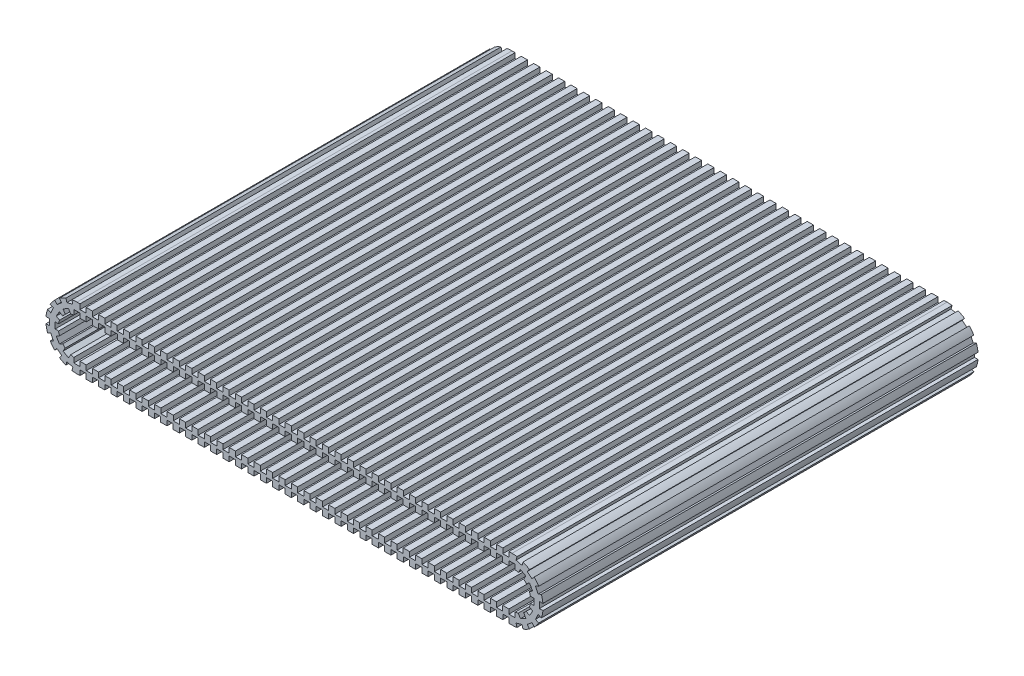
SolidWorks part; units mm, degrees
ref_plane "前视基准面" through (0, 0, 0) normal (0, 0, 1) x (1, 0, 0)
ref_plane "上视基准面" through (0, 0, 0) normal (0, 1, 0) x (1, 0, 0)
ref_plane "右视基准面" through (0, 0, 0) normal (1, 0, 0) x (0, 0, -1)
sketch "草图1" plane through (0, 0, 0) normal (0, 0, 1) x (1, 0, 0)
  line L0 (-175, 0) -> (175, 0) construction
  line L1 (-175, 25) -> (175, 25)
  line L2 (-175, -25) -> (175, -25)
  line L3 (-175, 0) -> (175, 0) construction
  line L4 (-175, 15) -> (175, 15)
  line L5 (-175, -15) -> (175, -15)
  arc A0 (-175, 25) -> (-175, -25) centre (-175, 0) ccw
  arc A1 (175, -25) -> (175, 25) centre (175, 0) ccw
  arc A2 (-175, 15) -> (-175, -15) centre (-175, 0) ccw
  arc A3 (175, -15) -> (175, 15) centre (175, 0) ccw
  point P3 (0, 0)
  point P8 (0, 0)
  dimension "D2" = 15
  dimension "D3" = 25
  dimension "D1" = 350
extrude "凸台-拉伸1" add sketch "草图1" along normal blind 350
sketch "草图2" plane through (0, 0, 350) normal (0, 0, 1) x (1, 0, 0)
  line L0 (-2.5, 25) -> (-2.5, 21)
  line L1 (175, 25) -> (-175, 25) construction
  line L2 (-2.5, 21) -> (2.5, 21)
  line L3 (2.5, 21) -> (2.5, 25)
  line L4 (-2.5, 25) -> (2.5, 25)
  line L5 (-12.5065, 25) -> (-7.5065, 25)
  line L6 (-7.5065, 21) -> (-7.5065, 25)
  line L7 (-12.5065, 21) -> (-7.5065, 21)
  line L8 (-12.5065, 25) -> (-12.5065, 21)
  line L9 (-22.513, 25) -> (-17.513, 25)
  line L10 (-17.513, 21) -> (-17.513, 25)
  line L11 (-22.513, 21) -> (-17.513, 21)
  line L12 (-22.513, 25) -> (-22.513, 21)
  line L13 (-32.5195, 25) -> (-27.5195, 25)
  line L14 (-27.5195, 21) -> (-27.5195, 25)
  line L15 (-32.5195, 21) -> (-27.5195, 21)
  line L16 (-32.5195, 25) -> (-32.5195, 21)
  line L17 (-42.526, 25) -> (-37.526, 25)
  line L18 (-37.526, 21) -> (-37.526, 25)
  line L19 (-42.526, 21) -> (-37.526, 21)
  line L20 (-42.526, 25) -> (-42.526, 21)
  line L21 (-52.5325, 25) -> (-47.5325, 25)
  line L22 (-47.5325, 21) -> (-47.5325, 25)
  line L23 (-52.5325, 21) -> (-47.5325, 21)
  line L24 (-52.5325, 25) -> (-52.5325, 21)
  line L25 (-62.539, 25) -> (-57.539, 25)
  line L26 (-57.539, 21) -> (-57.539, 25)
  line L27 (-62.539, 21) -> (-57.539, 21)
  line L28 (-62.539, 25) -> (-62.539, 21)
  line L29 (-72.5455, 25) -> (-67.5455, 25)
  line L30 (-67.5455, 21) -> (-67.5455, 25)
  line L31 (-72.5455, 21) -> (-67.5455, 21)
  line L32 (-72.5455, 25) -> (-72.5455, 21)
  line L33 (-82.552, 25) -> (-77.552, 25)
  line L34 (-77.552, 21) -> (-77.552, 25)
  line L35 (-82.552, 21) -> (-77.552, 21)
  line L36 (-82.552, 25) -> (-82.552, 21)
  line L37 (-92.5585, 25) -> (-87.5585, 25)
  line L38 (-87.5585, 21) -> (-87.5585, 25)
  line L39 (-92.5585, 21) -> (-87.5585, 21)
  line L40 (-92.5585, 25) -> (-92.5585, 21)
  line L41 (-102.5649, 25) -> (-97.5649, 25)
  line L42 (-97.5649, 21) -> (-97.5649, 25)
  line L43 (-102.5649, 21) -> (-97.5649, 21)
  line L44 (-102.5649, 25) -> (-102.5649, 21)
  line L45 (0, 0) -> (0, 11.574) construction
  line L46 (0, 0) -> (13.4491, 0) construction
  line L47 (102.5649, 25) -> (102.5649, 21)
  line L48 (102.5649, 21) -> (97.5649, 21)
  line L49 (97.5649, 21) -> (97.5649, 25)
  line L50 (102.5649, 25) -> (97.5649, 25)
  line L51 (92.5585, 25) -> (92.5585, 21)
  line L52 (92.5585, 21) -> (87.5585, 21)
  line L53 (87.5585, 21) -> (87.5585, 25)
  line L54 (92.5585, 25) -> (87.5585, 25)
  line L55 (82.552, 25) -> (82.552, 21)
  line L56 (82.552, 21) -> (77.552, 21)
  line L57 (77.552, 21) -> (77.552, 25)
  line L58 (82.552, 25) -> (77.552, 25)
  line L59 (72.5455, 25) -> (72.5455, 21)
  line L60 (72.5455, 21) -> (67.5455, 21)
  line L61 (67.5455, 21) -> (67.5455, 25)
  line L62 (72.5455, 25) -> (67.5455, 25)
  line L63 (62.539, 25) -> (62.539, 21)
  line L64 (62.539, 21) -> (57.539, 21)
  line L65 (57.539, 21) -> (57.539, 25)
  line L66 (62.539, 25) -> (57.539, 25)
  line L67 (52.5325, 25) -> (52.5325, 21)
  line L68 (52.5325, 21) -> (47.5325, 21)
  line L69 (47.5325, 21) -> (47.5325, 25)
  line L70 (52.5325, 25) -> (47.5325, 25)
  line L71 (42.526, 25) -> (42.526, 21)
  line L72 (42.526, 21) -> (37.526, 21)
  line L73 (37.526, 21) -> (37.526, 25)
  line L74 (42.526, 25) -> (37.526, 25)
  line L75 (32.5195, 25) -> (32.5195, 21)
  line L76 (32.5195, 21) -> (27.5195, 21)
  line L77 (27.5195, 21) -> (27.5195, 25)
  line L78 (32.5195, 25) -> (27.5195, 25)
  line L79 (22.513, 25) -> (22.513, 21)
  line L80 (22.513, 21) -> (17.513, 21)
  line L81 (17.513, 21) -> (17.513, 25)
  line L82 (22.513, 25) -> (17.513, 25)
  line L83 (12.5065, 25) -> (12.5065, 21)
  line L84 (12.5065, 21) -> (7.5065, 21)
  line L85 (7.5065, 21) -> (7.5065, 25)
  line L86 (12.5065, 25) -> (7.5065, 25)
  line L87 (-7.5065, 15) -> (-7.5065, 19)
  line L88 (175, 15) -> (-175, 15) construction
  line L89 (-7.5065, 19) -> (-2.5065, 19)
  line L90 (-2.5065, 19) -> (-2.5065, 15)
  line L91 (-2.5065, 15) -> (-7.5065, 15)
  line L92 (-12.5065, 15) -> (-17.5065, 15)
  line L93 (-17.5065, 15) -> (-17.5065, 19)
  line L94 (-17.5065, 19) -> (-12.5065, 19)
  line L95 (-12.5065, 19) -> (-12.5065, 15)
  line L96 (-22.5065, 15) -> (-27.5065, 15)
  line L97 (-27.5065, 15) -> (-27.5065, 19)
  line L98 (-27.5065, 19) -> (-22.5065, 19)
  line L99 (-22.5065, 19) -> (-22.5065, 15)
  line L100 (-32.5065, 15) -> (-37.5065, 15)
  line L101 (-37.5065, 15) -> (-37.5065, 19)
  line L102 (-37.5065, 19) -> (-32.5065, 19)
  line L103 (-32.5065, 19) -> (-32.5065, 15)
  line L104 (-42.5065, 15) -> (-47.5065, 15)
  line L105 (-47.5065, 15) -> (-47.5065, 19)
  line L106 (-47.5065, 19) -> (-42.5065, 19)
  line L107 (-42.5065, 19) -> (-42.5065, 15)
  line L108 (-52.5065, 15) -> (-57.5065, 15)
  line L109 (-57.5065, 15) -> (-57.5065, 19)
  line L110 (-57.5065, 19) -> (-52.5065, 19)
  line L111 (-52.5065, 19) -> (-52.5065, 15)
  line L112 (-62.5065, 15) -> (-67.5065, 15)
  line L113 (-67.5065, 15) -> (-67.5065, 19)
  line L114 (-67.5065, 19) -> (-62.5065, 19)
  line L115 (-62.5065, 19) -> (-62.5065, 15)
  line L116 (-72.5065, 15) -> (-77.5065, 15)
  line L117 (-77.5065, 15) -> (-77.5065, 19)
  line L118 (-77.5065, 19) -> (-72.5065, 19)
  line L119 (-72.5065, 19) -> (-72.5065, 15)
  line L120 (-82.5065, 15) -> (-87.5065, 15)
  line L121 (-87.5065, 15) -> (-87.5065, 19)
  line L122 (-87.5065, 19) -> (-82.5065, 19)
  line L123 (-82.5065, 19) -> (-82.5065, 15)
  line L124 (-92.5065, 15) -> (-97.5065, 15)
  line L125 (-97.5065, 15) -> (-97.5065, 19)
  line L126 (-97.5065, 19) -> (-92.5065, 19)
  line L127 (-92.5065, 19) -> (-92.5065, 15)
  line L128 (92.5065, 19) -> (92.5065, 15)
  line L129 (97.5065, 19) -> (92.5065, 19)
  line L130 (97.5065, 15) -> (97.5065, 19)
  line L131 (92.5065, 15) -> (97.5065, 15)
  line L132 (82.5065, 19) -> (82.5065, 15)
  line L133 (87.5065, 19) -> (82.5065, 19)
  line L134 (87.5065, 15) -> (87.5065, 19)
  line L135 (82.5065, 15) -> (87.5065, 15)
  line L136 (72.5065, 19) -> (72.5065, 15)
  line L137 (77.5065, 19) -> (72.5065, 19)
  line L138 (77.5065, 15) -> (77.5065, 19)
  line L139 (72.5065, 15) -> (77.5065, 15)
  line L140 (62.5065, 19) -> (62.5065, 15)
  line L141 (67.5065, 19) -> (62.5065, 19)
  line L142 (67.5065, 15) -> (67.5065, 19)
  line L143 (62.5065, 15) -> (67.5065, 15)
  line L144 (52.5065, 19) -> (52.5065, 15)
  line L145 (57.5065, 19) -> (52.5065, 19)
  line L146 (57.5065, 15) -> (57.5065, 19)
  line L147 (52.5065, 15) -> (57.5065, 15)
  line L148 (42.5065, 19) -> (42.5065, 15)
  line L149 (47.5065, 19) -> (42.5065, 19)
  line L150 (47.5065, 15) -> (47.5065, 19)
  line L151 (42.5065, 15) -> (47.5065, 15)
  line L152 (32.5065, 19) -> (32.5065, 15)
  line L153 (37.5065, 19) -> (32.5065, 19)
  line L154 (37.5065, 15) -> (37.5065, 19)
  line L155 (32.5065, 15) -> (37.5065, 15)
  line L156 (22.5065, 19) -> (22.5065, 15)
  line L157 (27.5065, 19) -> (22.5065, 19)
  line L158 (27.5065, 15) -> (27.5065, 19)
  line L159 (22.5065, 15) -> (27.5065, 15)
  line L160 (12.5065, 19) -> (12.5065, 15)
  line L161 (17.5065, 19) -> (12.5065, 19)
  line L162 (17.5065, 15) -> (17.5065, 19)
  line L163 (12.5065, 15) -> (17.5065, 15)
  line L164 (2.5065, 15) -> (7.5065, 15)
  line L165 (2.5065, 19) -> (2.5065, 15)
  line L166 (7.5065, 19) -> (2.5065, 19)
  line L167 (7.5065, 15) -> (7.5065, 19)
  line L168 (7.5065, -15) -> (7.5065, -19)
  line L169 (7.5065, -19) -> (2.5065, -19)
  line L170 (2.5065, -19) -> (2.5065, -15)
  line L171 (2.5065, -15) -> (7.5065, -15)
  line L172 (12.5065, -15) -> (17.5065, -15)
  line L173 (17.5065, -15) -> (17.5065, -19)
  line L174 (17.5065, -19) -> (12.5065, -19)
  line L175 (12.5065, -19) -> (12.5065, -15)
  line L176 (22.5065, -15) -> (27.5065, -15)
  line L177 (27.5065, -15) -> (27.5065, -19)
  line L178 (27.5065, -19) -> (22.5065, -19)
  line L179 (22.5065, -19) -> (22.5065, -15)
  line L180 (32.5065, -15) -> (37.5065, -15)
  line L181 (37.5065, -15) -> (37.5065, -19)
  line L182 (37.5065, -19) -> (32.5065, -19)
  line L183 (32.5065, -19) -> (32.5065, -15)
  line L184 (42.5065, -15) -> (47.5065, -15)
  line L185 (47.5065, -15) -> (47.5065, -19)
  line L186 (47.5065, -19) -> (42.5065, -19)
  line L187 (42.5065, -19) -> (42.5065, -15)
  line L188 (52.5065, -15) -> (57.5065, -15)
  line L189 (57.5065, -15) -> (57.5065, -19)
  line L190 (57.5065, -19) -> (52.5065, -19)
  line L191 (52.5065, -19) -> (52.5065, -15)
  line L192 (62.5065, -15) -> (67.5065, -15)
  line L193 (67.5065, -15) -> (67.5065, -19)
  line L194 (67.5065, -19) -> (62.5065, -19)
  line L195 (62.5065, -19) -> (62.5065, -15)
  line L196 (72.5065, -15) -> (77.5065, -15)
  line L197 (77.5065, -15) -> (77.5065, -19)
  line L198 (77.5065, -19) -> (72.5065, -19)
  line L199 (72.5065, -19) -> (72.5065, -15)
  line L200 (82.5065, -15) -> (87.5065, -15)
  line L201 (87.5065, -15) -> (87.5065, -19)
  line L202 (87.5065, -19) -> (82.5065, -19)
  line L203 (82.5065, -19) -> (82.5065, -15)
  line L204 (92.5065, -15) -> (97.5065, -15)
  line L205 (97.5065, -15) -> (97.5065, -19)
  line L206 (97.5065, -19) -> (92.5065, -19)
  line L207 (92.5065, -19) -> (92.5065, -15)
  line L208 (-92.5065, -19) -> (-92.5065, -15)
  line L209 (-97.5065, -19) -> (-92.5065, -19)
  line L210 (-97.5065, -15) -> (-97.5065, -19)
  line L211 (-92.5065, -15) -> (-97.5065, -15)
  line L212 (-82.5065, -19) -> (-82.5065, -15)
  line L213 (-87.5065, -19) -> (-82.5065, -19)
  line L214 (-87.5065, -15) -> (-87.5065, -19)
  line L215 (-82.5065, -15) -> (-87.5065, -15)
  line L216 (-72.5065, -19) -> (-72.5065, -15)
  line L217 (-77.5065, -19) -> (-72.5065, -19)
  line L218 (-77.5065, -15) -> (-77.5065, -19)
  line L219 (-72.5065, -15) -> (-77.5065, -15)
  line L220 (-62.5065, -19) -> (-62.5065, -15)
  line L221 (-67.5065, -19) -> (-62.5065, -19)
  line L222 (-67.5065, -15) -> (-67.5065, -19)
  line L223 (-62.5065, -15) -> (-67.5065, -15)
  line L224 (-52.5065, -19) -> (-52.5065, -15)
  line L225 (-57.5065, -19) -> (-52.5065, -19)
  line L226 (-57.5065, -15) -> (-57.5065, -19)
  line L227 (-52.5065, -15) -> (-57.5065, -15)
  line L228 (-42.5065, -19) -> (-42.5065, -15)
  line L229 (-47.5065, -19) -> (-42.5065, -19)
  line L230 (-47.5065, -15) -> (-47.5065, -19)
  line L231 (-42.5065, -15) -> (-47.5065, -15)
  line L232 (-32.5065, -19) -> (-32.5065, -15)
  line L233 (-37.5065, -19) -> (-32.5065, -19)
  line L234 (-37.5065, -15) -> (-37.5065, -19)
  line L235 (-32.5065, -15) -> (-37.5065, -15)
  line L236 (-22.5065, -19) -> (-22.5065, -15)
  line L237 (-27.5065, -19) -> (-22.5065, -19)
  line L238 (-27.5065, -15) -> (-27.5065, -19)
  line L239 (-22.5065, -15) -> (-27.5065, -15)
  line L240 (-12.5065, -19) -> (-12.5065, -15)
  line L241 (-17.5065, -19) -> (-12.5065, -19)
  line L242 (-17.5065, -15) -> (-17.5065, -19)
  line L243 (-12.5065, -15) -> (-17.5065, -15)
  line L244 (-2.5065, -15) -> (-7.5065, -15)
  line L245 (-2.5065, -19) -> (-2.5065, -15)
  line L246 (-7.5065, -19) -> (-2.5065, -19)
  line L247 (-7.5065, -15) -> (-7.5065, -19)
  line L248 (12.5065, -25) -> (7.5065, -25)
  line L249 (7.5065, -21) -> (7.5065, -25)
  line L250 (12.5065, -21) -> (7.5065, -21)
  line L251 (12.5065, -25) -> (12.5065, -21)
  line L252 (22.513, -25) -> (17.513, -25)
  line L253 (17.513, -21) -> (17.513, -25)
  line L254 (22.513, -21) -> (17.513, -21)
  line L255 (22.513, -25) -> (22.513, -21)
  line L256 (32.5195, -25) -> (27.5195, -25)
  line L257 (27.5195, -21) -> (27.5195, -25)
  line L258 (32.5195, -21) -> (27.5195, -21)
  line L259 (32.5195, -25) -> (32.5195, -21)
  line L260 (42.526, -25) -> (37.526, -25)
  line L261 (37.526, -21) -> (37.526, -25)
  line L262 (42.526, -21) -> (37.526, -21)
  line L263 (42.526, -25) -> (42.526, -21)
  line L264 (52.5325, -25) -> (47.5325, -25)
  line L265 (47.5325, -21) -> (47.5325, -25)
  line L266 (52.5325, -21) -> (47.5325, -21)
  line L267 (52.5325, -25) -> (52.5325, -21)
  line L268 (62.539, -25) -> (57.539, -25)
  line L269 (57.539, -21) -> (57.539, -25)
  line L270 (62.539, -21) -> (57.539, -21)
  line L271 (62.539, -25) -> (62.539, -21)
  line L272 (72.5455, -25) -> (67.5455, -25)
  line L273 (67.5455, -21) -> (67.5455, -25)
  line L274 (72.5455, -21) -> (67.5455, -21)
  line L275 (72.5455, -25) -> (72.5455, -21)
  line L276 (82.552, -25) -> (77.552, -25)
  line L277 (77.552, -21) -> (77.552, -25)
  line L278 (82.552, -21) -> (77.552, -21)
  line L279 (82.552, -25) -> (82.552, -21)
  line L280 (92.5585, -25) -> (87.5585, -25)
  line L281 (87.5585, -21) -> (87.5585, -25)
  line L282 (92.5585, -21) -> (87.5585, -21)
  line L283 (92.5585, -25) -> (92.5585, -21)
  line L284 (102.5649, -25) -> (97.5649, -25)
  line L285 (97.5649, -21) -> (97.5649, -25)
  line L286 (102.5649, -21) -> (97.5649, -21)
  line L287 (102.5649, -25) -> (102.5649, -21)
  line L288 (-102.5649, -25) -> (-102.5649, -21)
  line L289 (-102.5649, -21) -> (-97.5649, -21)
  line L290 (-97.5649, -21) -> (-97.5649, -25)
  line L291 (-102.5649, -25) -> (-97.5649, -25)
  line L292 (-92.5585, -25) -> (-92.5585, -21)
  line L293 (-92.5585, -21) -> (-87.5585, -21)
  line L294 (-87.5585, -21) -> (-87.5585, -25)
  line L295 (-92.5585, -25) -> (-87.5585, -25)
  line L296 (-82.552, -25) -> (-82.552, -21)
  line L297 (-82.552, -21) -> (-77.552, -21)
  line L298 (-77.552, -21) -> (-77.552, -25)
  line L299 (-82.552, -25) -> (-77.552, -25)
  line L300 (-72.5455, -25) -> (-72.5455, -21)
  line L301 (-72.5455, -21) -> (-67.5455, -21)
  line L302 (-67.5455, -21) -> (-67.5455, -25)
  line L303 (-72.5455, -25) -> (-67.5455, -25)
  line L304 (-62.539, -25) -> (-62.539, -21)
  line L305 (-62.539, -21) -> (-57.539, -21)
  line L306 (-57.539, -21) -> (-57.539, -25)
  line L307 (-62.539, -25) -> (-57.539, -25)
  line L308 (-52.5325, -25) -> (-52.5325, -21)
  line L309 (-52.5325, -21) -> (-47.5325, -21)
  line L310 (-47.5325, -21) -> (-47.5325, -25)
  line L311 (-52.5325, -25) -> (-47.5325, -25)
  line L312 (-42.526, -25) -> (-42.526, -21)
  line L313 (-42.526, -21) -> (-37.526, -21)
  line L314 (-37.526, -21) -> (-37.526, -25)
  line L315 (-42.526, -25) -> (-37.526, -25)
  line L316 (-32.5195, -25) -> (-32.5195, -21)
  line L317 (-32.5195, -21) -> (-27.5195, -21)
  line L318 (-27.5195, -21) -> (-27.5195, -25)
  line L319 (-32.5195, -25) -> (-27.5195, -25)
  line L320 (-22.513, -25) -> (-22.513, -21)
  line L321 (-22.513, -21) -> (-17.513, -21)
  line L322 (-17.513, -21) -> (-17.513, -25)
  line L323 (-22.513, -25) -> (-17.513, -25)
  line L324 (-12.5065, -25) -> (-12.5065, -21)
  line L325 (-12.5065, -21) -> (-7.5065, -21)
  line L326 (-7.5065, -21) -> (-7.5065, -25)
  line L327 (-12.5065, -25) -> (-7.5065, -25)
  line L328 (-2.5, -25) -> (2.5, -25)
  line L329 (2.5, -21) -> (2.5, -25)
  line L330 (-2.5, -21) -> (2.5, -21)
  line L331 (-2.5, -25) -> (-2.5, -21)
  line L332 (-112.5649, 25) -> (-107.5649, 25)
  line L333 (-107.5649, 21) -> (-107.5649, 25)
  line L334 (-112.5649, 21) -> (-107.5649, 21)
  line L335 (-112.5649, 25) -> (-112.5649, 21)
  line L336 (-102.5065, 15) -> (-107.5065, 15)
  line L337 (-107.5065, 15) -> (-107.5065, 19)
  line L338 (-107.5065, 19) -> (-102.5065, 19)
  line L339 (-102.5065, 19) -> (-102.5065, 15)
  line L340 (-122.5649, 25) -> (-117.5649, 25)
  line L341 (-117.5649, 21) -> (-117.5649, 25)
  line L342 (-122.5649, 21) -> (-117.5649, 21)
  line L343 (-122.5649, 25) -> (-122.5649, 21)
  line L344 (-112.5065, 15) -> (-117.5065, 15)
  line L345 (-117.5065, 15) -> (-117.5065, 19)
  line L346 (-117.5065, 19) -> (-112.5065, 19)
  line L347 (-112.5065, 19) -> (-112.5065, 15)
  line L348 (-132.5649, 25) -> (-127.5649, 25)
  line L349 (-127.5649, 21) -> (-127.5649, 25)
  line L350 (-132.5649, 21) -> (-127.5649, 21)
  line L351 (-132.5649, 25) -> (-132.5649, 21)
  line L352 (-122.5065, 15) -> (-127.5065, 15)
  line L353 (-127.5065, 15) -> (-127.5065, 19)
  line L354 (-127.5065, 19) -> (-122.5065, 19)
  line L355 (-122.5065, 19) -> (-122.5065, 15)
  line L356 (-142.5649, 25) -> (-137.5649, 25)
  line L357 (-137.5649, 21) -> (-137.5649, 25)
  line L358 (-142.5649, 21) -> (-137.5649, 21)
  line L359 (-142.5649, 25) -> (-142.5649, 21)
  line L360 (-132.5065, 15) -> (-137.5065, 15)
  line L361 (-137.5065, 15) -> (-137.5065, 19)
  line L362 (-137.5065, 19) -> (-132.5065, 19)
  line L363 (-132.5065, 19) -> (-132.5065, 15)
  line L364 (-152.5649, 25) -> (-147.5649, 25)
  line L365 (-147.5649, 21) -> (-147.5649, 25)
  line L366 (-152.5649, 21) -> (-147.5649, 21)
  line L367 (-152.5649, 25) -> (-152.5649, 21)
  line L368 (-142.5065, 15) -> (-147.5065, 15)
  line L369 (-147.5065, 15) -> (-147.5065, 19)
  line L370 (-147.5065, 19) -> (-142.5065, 19)
  line L371 (-142.5065, 19) -> (-142.5065, 15)
  line L372 (-162.5649, 25) -> (-157.5649, 25)
  line L373 (-157.5649, 21) -> (-157.5649, 25)
  line L374 (-162.5649, 21) -> (-157.5649, 21)
  line L375 (-162.5649, 25) -> (-162.5649, 21)
  line L376 (-152.5065, 15) -> (-157.5065, 15)
  line L377 (-157.5065, 15) -> (-157.5065, 19)
  line L378 (-157.5065, 19) -> (-152.5065, 19)
  line L379 (-152.5065, 19) -> (-152.5065, 15)
  line L380 (-172.5649, 25) -> (-167.5649, 25)
  line L381 (-167.5649, 21) -> (-167.5649, 25)
  line L382 (-172.5649, 21) -> (-167.5649, 21)
  line L383 (-172.5649, 25) -> (-172.5649, 21)
  line L384 (-162.5065, 15) -> (-167.5065, 15)
  line L385 (-167.5065, 15) -> (-167.5065, 19)
  line L386 (-167.5065, 19) -> (-162.5065, 19)
  line L387 (-162.5065, 19) -> (-162.5065, 15)
  line L388 (112.5649, 25) -> (112.5649, 21)
  line L389 (112.5649, 21) -> (107.5649, 21)
  line L390 (107.5649, 21) -> (107.5649, 25)
  line L391 (112.5649, 25) -> (107.5649, 25)
  line L392 (102.5065, 19) -> (102.5065, 15)
  line L393 (102.5065, 15) -> (107.5065, 15)
  line L394 (107.5065, 15) -> (107.5065, 19)
  line L395 (107.5065, 19) -> (102.5065, 19)
  line L396 (122.5649, 25) -> (122.5649, 21)
  line L397 (122.5649, 21) -> (117.5649, 21)
  line L398 (117.5649, 21) -> (117.5649, 25)
  line L399 (122.5649, 25) -> (117.5649, 25)
  line L400 (112.5065, 19) -> (112.5065, 15)
  line L401 (112.5065, 15) -> (117.5065, 15)
  line L402 (117.5065, 15) -> (117.5065, 19)
  line L403 (117.5065, 19) -> (112.5065, 19)
  line L404 (132.5649, 25) -> (132.5649, 21)
  line L405 (132.5649, 21) -> (127.5649, 21)
  line L406 (127.5649, 21) -> (127.5649, 25)
  line L407 (132.5649, 25) -> (127.5649, 25)
  line L408 (122.5065, 19) -> (122.5065, 15)
  line L409 (122.5065, 15) -> (127.5065, 15)
  line L410 (127.5065, 15) -> (127.5065, 19)
  line L411 (127.5065, 19) -> (122.5065, 19)
  line L412 (142.5649, 25) -> (142.5649, 21)
  line L413 (142.5649, 21) -> (137.5649, 21)
  line L414 (137.5649, 21) -> (137.5649, 25)
  line L415 (142.5649, 25) -> (137.5649, 25)
  line L416 (132.5065, 19) -> (132.5065, 15)
  line L417 (132.5065, 15) -> (137.5065, 15)
  line L418 (137.5065, 15) -> (137.5065, 19)
  line L419 (137.5065, 19) -> (132.5065, 19)
  line L420 (152.5649, 25) -> (152.5649, 21)
  line L421 (152.5649, 21) -> (147.5649, 21)
  line L422 (147.5649, 21) -> (147.5649, 25)
  line L423 (152.5649, 25) -> (147.5649, 25)
  line L424 (142.5065, 19) -> (142.5065, 15)
  line L425 (142.5065, 15) -> (147.5065, 15)
  line L426 (147.5065, 15) -> (147.5065, 19)
  line L427 (147.5065, 19) -> (142.5065, 19)
  line L428 (162.5649, 25) -> (162.5649, 21)
  line L429 (162.5649, 21) -> (157.5649, 21)
  line L430 (157.5649, 21) -> (157.5649, 25)
  line L431 (162.5649, 25) -> (157.5649, 25)
  line L432 (152.5065, 19) -> (152.5065, 15)
  line L433 (152.5065, 15) -> (157.5065, 15)
  line L434 (157.5065, 15) -> (157.5065, 19)
  line L435 (157.5065, 19) -> (152.5065, 19)
  line L436 (172.5649, 25) -> (172.5649, 21)
  line L437 (172.5649, 21) -> (167.5649, 21)
  line L438 (167.5649, 21) -> (167.5649, 25)
  line L439 (172.5649, 25) -> (167.5649, 25)
  line L440 (162.5065, 19) -> (162.5065, 15)
  line L441 (162.5065, 15) -> (167.5065, 15)
  line L442 (167.5065, 15) -> (167.5065, 19)
  line L443 (167.5065, 19) -> (162.5065, 19)
  line L444 (112.5649, -25) -> (107.5649, -25)
  line L445 (107.5649, -21) -> (107.5649, -25)
  line L446 (112.5649, -21) -> (107.5649, -21)
  line L447 (112.5649, -25) -> (112.5649, -21)
  line L448 (102.5065, -15) -> (107.5065, -15)
  line L449 (107.5065, -15) -> (107.5065, -19)
  line L450 (107.5065, -19) -> (102.5065, -19)
  line L451 (102.5065, -19) -> (102.5065, -15)
  line L452 (122.5649, -25) -> (117.5649, -25)
  line L453 (117.5649, -21) -> (117.5649, -25)
  line L454 (122.5649, -21) -> (117.5649, -21)
  line L455 (122.5649, -25) -> (122.5649, -21)
  line L456 (112.5065, -15) -> (117.5065, -15)
  line L457 (117.5065, -15) -> (117.5065, -19)
  line L458 (117.5065, -19) -> (112.5065, -19)
  line L459 (112.5065, -19) -> (112.5065, -15)
  line L460 (132.5649, -25) -> (127.5649, -25)
  line L461 (127.5649, -21) -> (127.5649, -25)
  line L462 (132.5649, -21) -> (127.5649, -21)
  line L463 (132.5649, -25) -> (132.5649, -21)
  line L464 (122.5065, -15) -> (127.5065, -15)
  line L465 (127.5065, -15) -> (127.5065, -19)
  line L466 (127.5065, -19) -> (122.5065, -19)
  line L467 (122.5065, -19) -> (122.5065, -15)
  line L468 (142.5649, -25) -> (137.5649, -25)
  line L469 (137.5649, -21) -> (137.5649, -25)
  line L470 (142.5649, -21) -> (137.5649, -21)
  line L471 (142.5649, -25) -> (142.5649, -21)
  line L472 (132.5065, -15) -> (137.5065, -15)
  line L473 (137.5065, -15) -> (137.5065, -19)
  line L474 (137.5065, -19) -> (132.5065, -19)
  line L475 (132.5065, -19) -> (132.5065, -15)
  line L476 (152.5649, -25) -> (147.5649, -25)
  line L477 (147.5649, -21) -> (147.5649, -25)
  line L478 (152.5649, -21) -> (147.5649, -21)
  line L479 (152.5649, -25) -> (152.5649, -21)
  line L480 (142.5065, -15) -> (147.5065, -15)
  line L481 (147.5065, -15) -> (147.5065, -19)
  line L482 (147.5065, -19) -> (142.5065, -19)
  line L483 (142.5065, -19) -> (142.5065, -15)
  line L484 (162.5649, -25) -> (157.5649, -25)
  line L485 (157.5649, -21) -> (157.5649, -25)
  line L486 (162.5649, -21) -> (157.5649, -21)
  line L487 (162.5649, -25) -> (162.5649, -21)
  line L488 (152.5065, -15) -> (157.5065, -15)
  line L489 (157.5065, -15) -> (157.5065, -19)
  line L490 (157.5065, -19) -> (152.5065, -19)
  line L491 (152.5065, -19) -> (152.5065, -15)
  line L492 (172.5649, -25) -> (167.5649, -25)
  line L493 (167.5649, -21) -> (167.5649, -25)
  line L494 (172.5649, -21) -> (167.5649, -21)
  line L495 (172.5649, -25) -> (172.5649, -21)
  line L496 (162.5065, -15) -> (167.5065, -15)
  line L497 (167.5065, -15) -> (167.5065, -19)
  line L498 (167.5065, -19) -> (162.5065, -19)
  line L499 (162.5065, -19) -> (162.5065, -15)
  line L500 (-112.5649, -25) -> (-112.5649, -21)
  line L501 (-112.5649, -21) -> (-107.5649, -21)
  line L502 (-107.5649, -21) -> (-107.5649, -25)
  line L503 (-112.5649, -25) -> (-107.5649, -25)
  line L504 (-102.5065, -19) -> (-102.5065, -15)
  line L505 (-102.5065, -15) -> (-107.5065, -15)
  line L506 (-107.5065, -15) -> (-107.5065, -19)
  line L507 (-107.5065, -19) -> (-102.5065, -19)
  line L508 (-122.5649, -25) -> (-122.5649, -21)
  line L509 (-122.5649, -21) -> (-117.5649, -21)
  line L510 (-117.5649, -21) -> (-117.5649, -25)
  line L511 (-122.5649, -25) -> (-117.5649, -25)
  line L512 (-112.5065, -19) -> (-112.5065, -15)
  line L513 (-112.5065, -15) -> (-117.5065, -15)
  line L514 (-117.5065, -15) -> (-117.5065, -19)
  line L515 (-117.5065, -19) -> (-112.5065, -19)
  line L516 (-132.5649, -25) -> (-132.5649, -21)
  line L517 (-132.5649, -21) -> (-127.5649, -21)
  line L518 (-127.5649, -21) -> (-127.5649, -25)
  line L519 (-132.5649, -25) -> (-127.5649, -25)
  line L520 (-122.5065, -19) -> (-122.5065, -15)
  line L521 (-122.5065, -15) -> (-127.5065, -15)
  line L522 (-127.5065, -15) -> (-127.5065, -19)
  line L523 (-127.5065, -19) -> (-122.5065, -19)
  line L524 (-142.5649, -25) -> (-142.5649, -21)
  line L525 (-142.5649, -21) -> (-137.5649, -21)
  line L526 (-137.5649, -21) -> (-137.5649, -25)
  line L527 (-142.5649, -25) -> (-137.5649, -25)
  line L528 (-132.5065, -19) -> (-132.5065, -15)
  line L529 (-132.5065, -15) -> (-137.5065, -15)
  line L530 (-137.5065, -15) -> (-137.5065, -19)
  line L531 (-137.5065, -19) -> (-132.5065, -19)
  line L532 (-152.5649, -25) -> (-152.5649, -21)
  line L533 (-152.5649, -21) -> (-147.5649, -21)
  line L534 (-147.5649, -21) -> (-147.5649, -25)
  line L535 (-152.5649, -25) -> (-147.5649, -25)
  line L536 (-142.5065, -19) -> (-142.5065, -15)
  line L537 (-142.5065, -15) -> (-147.5065, -15)
  line L538 (-147.5065, -15) -> (-147.5065, -19)
  line L539 (-147.5065, -19) -> (-142.5065, -19)
  line L540 (-162.5649, -25) -> (-162.5649, -21)
  line L541 (-162.5649, -21) -> (-157.5649, -21)
  line L542 (-157.5649, -21) -> (-157.5649, -25)
  line L543 (-162.5649, -25) -> (-157.5649, -25)
  line L544 (-152.5065, -19) -> (-152.5065, -15)
  line L545 (-152.5065, -15) -> (-157.5065, -15)
  line L546 (-157.5065, -15) -> (-157.5065, -19)
  line L547 (-157.5065, -19) -> (-152.5065, -19)
  line L548 (-172.5649, -25) -> (-172.5649, -21)
  line L549 (-172.5649, -21) -> (-167.5649, -21)
  line L550 (-167.5649, -21) -> (-167.5649, -25)
  line L551 (-172.5649, -25) -> (-167.5649, -25)
  line L552 (-162.5065, -19) -> (-162.5065, -15)
  line L553 (-162.5065, -15) -> (-167.5065, -15)
  line L554 (-167.5065, -15) -> (-167.5065, -19)
  line L555 (-167.5065, -19) -> (-162.5065, -19)
  point P4 (0, 21)
  dimension "D1" = 5
  dimension "D2" = 4
  dimension "D3" = 5
  dimension "D4" = 4
  dimension "D5" = 11
  dimension "D7" = 8
  dimension "D6" = 10
  dimension "D8" = 8
  dimension "D9" = 8
  dimension "D10" = 8
extrude "切除-拉伸1" cut sketch "草图2" against normal blind 350
sketch "草图3" plane through (0, 0, 0) normal (0, 0, -1) x (-1, 0, 0)
  line L0 (187.2863, -4.4503) -> (184.7863, -8.7804)
  line L1 (187.5, 2.5) -> (192.5, 2.5)
  line L2 (187.5, 2.5) -> (187.5, -2.5)
  line L3 (187.5, -2.5) -> (192.5, -2.5)
  line L4 (192.5, 2.5) -> (192.5, -2.5)
  line L5 (190, -2.5) -> (190, 2.5) construction
  line L6 (187.5, 0) -> (192.5, 0) construction
  line L7 (187.2863, -4.4503) -> (191.6164, -6.9503)
  line L8 (191.6164, -6.9503) -> (189.1164, -11.2804)
  line L9 (184.7863, -8.7804) -> (189.1164, -11.2804)
  line L10 (183.626, -10.3626) -> (179.2959, -12.8626)
  line L11 (183.626, -10.3626) -> (186.126, -14.6927)
  line L12 (186.126, -14.6927) -> (181.7959, -17.1927)
  line L13 (179.2959, -12.8626) -> (181.7959, -17.1927)
  line L14 (177.5, -13.6527) -> (172.5, -13.6527)
  line L15 (177.5, -13.6527) -> (177.5, -18.6527)
  line L16 (177.5, -18.6527) -> (172.5, -18.6527)
  line L17 (172.5, -13.6527) -> (172.5, -18.6527)
  line L18 (175, 0) -> (149.4993, 0) construction
  line L19 (177.5, 13.6527) -> (177.5, 18.6527)
  line L20 (177.5, 18.6527) -> (172.5, 18.6527)
  line L21 (172.5, 13.6527) -> (172.5, 18.6527)
  line L22 (177.5, 13.6527) -> (172.5, 13.6527)
  line L23 (183.626, 10.3626) -> (186.126, 14.6927)
  line L24 (186.126, 14.6927) -> (181.7959, 17.1927)
  line L25 (179.2959, 12.8626) -> (181.7959, 17.1927)
  line L26 (183.626, 10.3626) -> (179.2959, 12.8626)
  line L27 (187.2863, 4.4503) -> (191.6164, 6.9503)
  line L28 (191.6164, 6.9503) -> (189.1164, 11.2804)
  line L29 (184.7863, 8.7804) -> (189.1164, 11.2804)
  line L30 (187.2863, 4.4503) -> (184.7863, 8.7804)
  line L31 (0, 0) -> (0, -79.928) construction
  line L32 (195.9953, -7.0318) -> (193.8822, -11.5634)
  line L33 (197, 2.5) -> (203, 2.5)
  line L34 (197, 2.5) -> (197, -2.5)
  line L35 (197, -2.5) -> (203, -2.5)
  line L36 (203, 2.5) -> (203, -2.5)
  line L37 (200, -2.5) -> (200, 2.5) construction
  line L38 (197, 0) -> (203, 0) construction
  line L39 (195.9953, -7.0318) -> (201.4332, -9.5675)
  line L40 (201.4332, -9.5675) -> (199.3201, -14.0991)
  line L41 (193.8822, -11.5634) -> (199.3201, -14.0991)
  line L42 (191.0564, -15.246) -> (187.2262, -18.4599)
  line L43 (191.0564, -15.246) -> (194.9132, -19.8423)
  line L44 (194.9132, -19.8423) -> (191.0829, -23.0562)
  line L45 (187.2262, -18.4599) -> (191.0829, -23.0562)
  line L46 (183.1088, -20.6033) -> (178.2792, -21.8974)
  line L47 (183.1088, -20.6033) -> (184.6617, -26.3989)
  line L48 (184.6617, -26.3989) -> (179.8321, -27.693)
  line L49 (178.2792, -21.8974) -> (179.8321, -27.693)
  line L50 (183.1088, 20.6033) -> (184.6617, 26.3989)
  line L51 (184.6617, 26.3989) -> (179.8321, 27.693)
  line L52 (178.2792, 21.8974) -> (179.8321, 27.693)
  line L53 (183.1088, 20.6033) -> (178.2792, 21.8974)
  line L54 (191.0564, 15.246) -> (194.9132, 19.8423)
  line L55 (194.9132, 19.8423) -> (191.0829, 23.0562)
  line L56 (187.2262, 18.4599) -> (191.0829, 23.0562)
  line L57 (191.0564, 15.246) -> (187.2262, 18.4599)
  line L58 (195.9953, 7.0318) -> (201.4332, 9.5675)
  line L59 (201.4332, 9.5675) -> (199.3201, 14.0991)
  line L60 (193.8822, 11.5634) -> (199.3201, 14.0991)
  line L61 (195.9953, 7.0318) -> (193.8822, 11.5634)
  line L62 (-197, 0) -> (-203, 0) construction
  line L63 (-200, -2.5) -> (-200, 2.5) construction
  line L64 (-175, 0) -> (-149.4993, 0) construction
  line L65 (-187.5, 0) -> (-192.5, 0) construction
  line L66 (-190, -2.5) -> (-190, 2.5) construction
  line L67 (-195.9953, 7.0318) -> (-193.8822, 11.5634)
  line L68 (-193.8822, 11.5634) -> (-199.3201, 14.0991)
  line L69 (-201.4332, 9.5675) -> (-199.3201, 14.0991)
  line L70 (-195.9953, 7.0318) -> (-201.4332, 9.5675)
  line L71 (-191.0564, 15.246) -> (-187.2262, 18.4599)
  line L72 (-187.2262, 18.4599) -> (-191.0829, 23.0562)
  line L73 (-194.9132, 19.8423) -> (-191.0829, 23.0562)
  line L74 (-191.0564, 15.246) -> (-194.9132, 19.8423)
  line L75 (-183.1088, 20.6033) -> (-178.2792, 21.8974)
  line L76 (-178.2792, 21.8974) -> (-179.8321, 27.693)
  line L77 (-184.6617, 26.3989) -> (-179.8321, 27.693)
  line L78 (-183.1088, 20.6033) -> (-184.6617, 26.3989)
  line L79 (-178.2792, -21.8974) -> (-179.8321, -27.693)
  line L80 (-184.6617, -26.3989) -> (-179.8321, -27.693)
  line L81 (-183.1088, -20.6033) -> (-184.6617, -26.3989)
  line L82 (-183.1088, -20.6033) -> (-178.2792, -21.8974)
  line L83 (-187.2262, -18.4599) -> (-191.0829, -23.0562)
  line L84 (-194.9132, -19.8423) -> (-191.0829, -23.0562)
  line L85 (-191.0564, -15.246) -> (-194.9132, -19.8423)
  line L86 (-191.0564, -15.246) -> (-187.2262, -18.4599)
  line L87 (-193.8822, -11.5634) -> (-199.3201, -14.0991)
  line L88 (-201.4332, -9.5675) -> (-199.3201, -14.0991)
  line L89 (-195.9953, -7.0318) -> (-201.4332, -9.5675)
  line L90 (-203, 2.5) -> (-203, -2.5)
  line L91 (-197, -2.5) -> (-203, -2.5)
  line L92 (-197, 2.5) -> (-197, -2.5)
  line L93 (-197, 2.5) -> (-203, 2.5)
  line L94 (-195.9953, -7.0318) -> (-193.8822, -11.5634)
  line L95 (-187.2863, 4.4503) -> (-184.7863, 8.7804)
  line L96 (-184.7863, 8.7804) -> (-189.1164, 11.2804)
  line L97 (-191.6164, 6.9503) -> (-189.1164, 11.2804)
  line L98 (-187.2863, 4.4503) -> (-191.6164, 6.9503)
  line L99 (-183.626, 10.3626) -> (-179.2959, 12.8626)
  line L100 (-179.2959, 12.8626) -> (-181.7959, 17.1927)
  line L101 (-186.126, 14.6927) -> (-181.7959, 17.1927)
  line L102 (-183.626, 10.3626) -> (-186.126, 14.6927)
  line L103 (-177.5, 13.6527) -> (-172.5, 13.6527)
  line L104 (-172.5, 13.6527) -> (-172.5, 18.6527)
  line L105 (-177.5, 18.6527) -> (-172.5, 18.6527)
  line L106 (-177.5, 13.6527) -> (-177.5, 18.6527)
  line L107 (-172.5, -13.6527) -> (-172.5, -18.6527)
  line L108 (-177.5, -18.6527) -> (-172.5, -18.6527)
  line L109 (-177.5, -13.6527) -> (-177.5, -18.6527)
  line L110 (-177.5, -13.6527) -> (-172.5, -13.6527)
  line L111 (-179.2959, -12.8626) -> (-181.7959, -17.1927)
  line L112 (-186.126, -14.6927) -> (-181.7959, -17.1927)
  line L113 (-183.626, -10.3626) -> (-186.126, -14.6927)
  line L114 (-183.626, -10.3626) -> (-179.2959, -12.8626)
  line L115 (-184.7863, -8.7804) -> (-189.1164, -11.2804)
  line L116 (-191.6164, -6.9503) -> (-189.1164, -11.2804)
  line L117 (-187.2863, -4.4503) -> (-191.6164, -6.9503)
  line L118 (-192.5, 2.5) -> (-192.5, -2.5)
  line L119 (-187.5, -2.5) -> (-192.5, -2.5)
  line L120 (-187.5, 2.5) -> (-187.5, -2.5)
  line L121 (-187.5, 2.5) -> (-192.5, 2.5)
  line L122 (-187.2863, -4.4503) -> (-184.7863, -8.7804)
  circle A0 centre (175, 0) radius 15 construction
  arc A1 (175, -25) -> (175, 25) centre (175, 0) ccw construction
  circle A2 centre (-175, 0) radius 15 construction
  point P3 (190, 0)
  point P34 (200, 0)
  point P138 (-200, 0)
  point P139 (-190, 0)
  dimension "D1" = 5
  dimension "D2" = 2.5
  dimension "D4" = 5
  dimension "D5" = 3
  dimension "D3" = 4
  dimension "D6" = 4
extrude "切除-拉伸2" cut sketch "草图3" against normal blind 870
